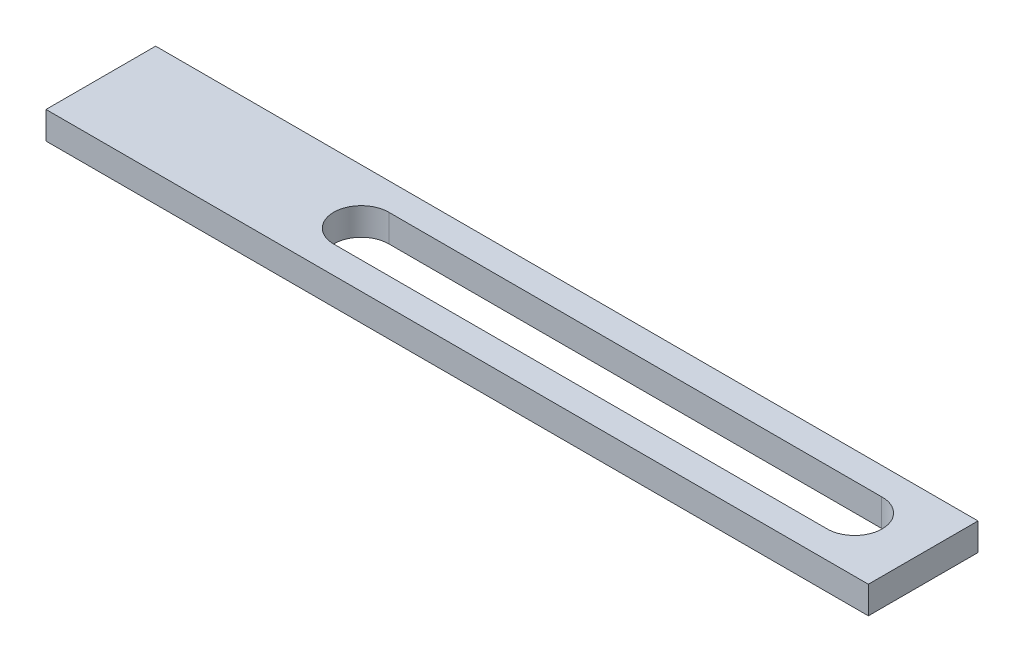
SolidWorks part; units mm, degrees
ref_plane "Спереди" through (0, 0, 0) normal (0, 0, 1) x (1, 0, 0)
ref_plane "Сверху" through (0, 0, 0) normal (0, 1, 0) x (1, 0, 0)
ref_plane "Справа" through (0, 0, 0) normal (1, 0, 0) x (0, 0, -1)
sketch "Эскиз1" plane through (0, 0, 0) normal (0, 1, 0) x (1, 0, 0)
  line L1 (0, 0) -> (300, 0)
  line L2 (0, 0) -> (0, 40)
  line L3 (0, 40) -> (300, 40)
  line L4 (300, 0) -> (300, 40)
extrude "Бобышка-Вытянуть1" add sketch "Эскиз1" along normal blind 10
sketch "Эскиз2" plane through (0, 10, 0) normal (0, 1, 0) x (1, 0, 0)
  line L0 (95, 9.95) -> (274.7214, 9.9539)
  line L1 (95, 30.05) -> (274.7214, 30.0461)
  arc A0 (95, 30.05) -> (95, 9.95) centre (95, 20) ccw
  arc A1 (274.7214, 30.0461) -> (274.7214, 9.9539) centre (275, 20) cw
  point P6 (271.9903, 20)
  point P7 (0, 0)
extrude "Вырез-Вытянуть1" cut sketch "Эскиз2" against normal up to next
